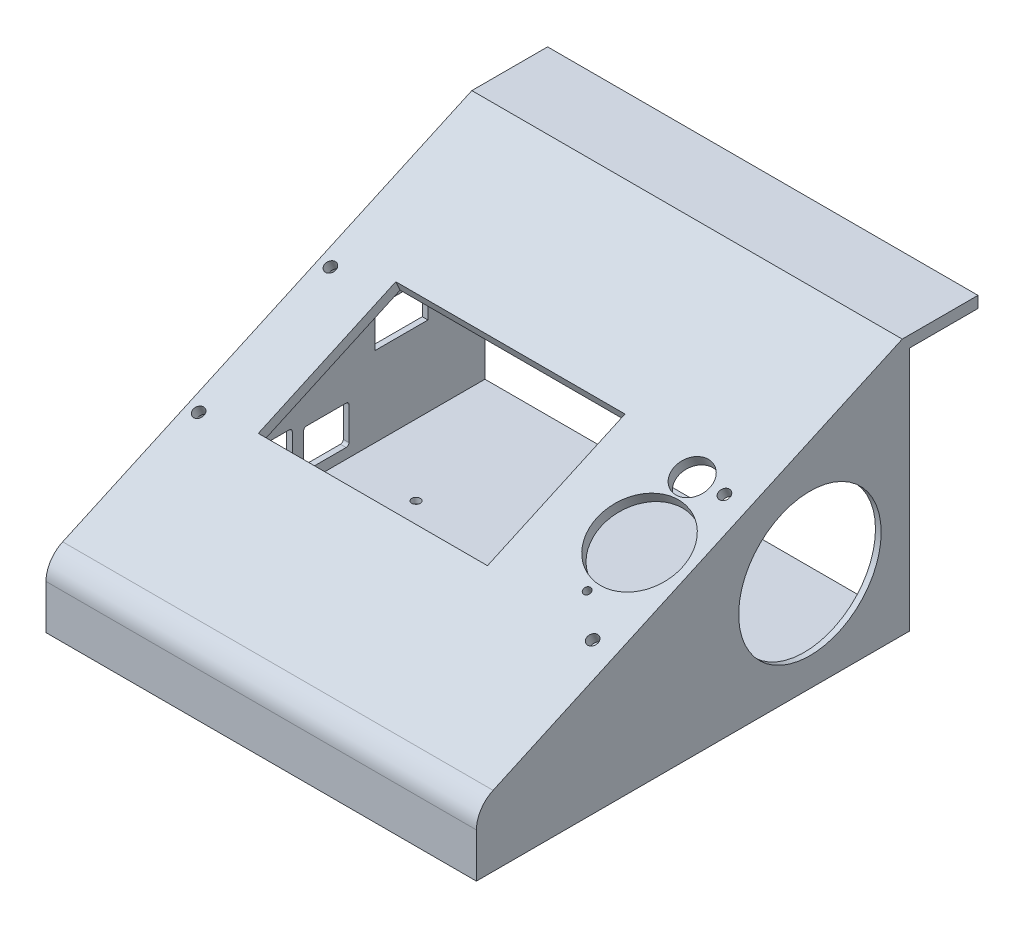
SolidWorks part; units mm, degrees
ref_plane "Front Plane" through (0, 0, 0) normal (0, 0, 1) x (1, 0, 0)
ref_plane "Top Plane" through (0, 0, 0) normal (0, 1, 0) x (1, 0, 0)
ref_plane "Right Plane" through (0, 0, 0) normal (1, 0, 0) x (0, 0, -1)
sketch "Sketch1" plane through (0, 0, 0) normal (0, 0, 1) x (1, 0, 0)
  line L0 (0, 0) -> (0, 86) construction
  dimension "D1" = 86
sketch "Sketch2" plane through (0, 0, 0) normal (0, 1, 0) x (1, 0, 0)
  line L0 (75.5, 0) -> (-75.5, 0)
  line L1 (-75.5, 0) -> (-75.5, -152)
  line L2 (-75.5, -152) -> (75.5, -152)
  line L3 (75.5, -152) -> (75.5, 0)
  point P4 (0, 0)
  dimension "D1" = 151
  dimension "D2" = 152
extrude "Boss-Extrude1" add sketch "Sketch2" along normal blind 2
sketch "Sketch3" plane through (0, 2, 0) normal (0, 1, 0) x (1, 0, 0)
  line L0 (-75.5, 0) -> (-75.5, -152) construction
  line L1 (-75.5, 0) -> (-75.5, -152)
  line L2 (-75.5, -152) -> (75.5, -152) construction
  line L3 (-75.5, -152) -> (75.5, -152)
  line L4 (75.5, -152) -> (75.5, 0) construction
  line L5 (75.5, -152) -> (75.5, 0)
extrude "Extrude-Thin1" add sketch "Sketch3" along normal blind 20 thin thin type one direction reverse wall 2
sketch "Sketch4" plane through (0, 0, 0) normal (1, 0, 0) x (0, 0, -1)
  line L0 (0, 86) -> (23.9691, 86)
  line L1 (0, 0) -> (0, 86) construction
  line L2 (23.9691, 86) -> (23.9691, 90)
  line L9 (23.9691, 90) -> (0, 90)
  line L10 (0, 90) -> (-2.6061, 90)
  line L11 (-2.6061, 90) -> (-152, 22)
  line L12 (-2.6061, 86) -> (-143.2121, 22)
  line L13 (-152, 22) -> (0, 22) construction
  line L14 (-143.2121, 22) -> (-152, 22)
  line L15 (-2.6061, 86) -> (0, 86)
  dimension "D1" = 4
  dimension "D2" = 8.7879
extrude "Boss-Extrude3" add sketch "Sketch4" against normal up to surface (151 mm away) from surface at 75.5 up to face at (-75.5, 11, 76) starting at face at (75.5, 11, 76)
sketch "Sketch6" plane through (75.5, 0, 0) normal (1, 0, 0) x (0, 0, -1)
  line L0 (0, 22) -> (-143.2121, 22)
  line L1 (-143.2121, 22) -> (-2.6061, 86)
  line L2 (-2.6061, 86) -> (0, 86)
  line L3 (0, 0) -> (0, 86) construction
  line L4 (-2.6061, 86) -> (23.9691, 86) construction
  line L5 (0, 86) -> (0, 22)
extrude "Boss-Extrude4" add sketch "Sketch6" against normal blind 2
sketch "Sketch7" plane through (-75.5, 0, 0) normal (-1, 0, 0) x (0, 0, 1)
  line L4 (0, 86) -> (0, 22)
  line L5 (0, 22) -> (143.2121, 22)
  line L6 (143.2121, 22) -> (2.6061, 86)
  line L7 (2.6061, 86) -> (0, 86)
extrude "Boss-Extrude5" add sketch "Sketch7" against normal blind 2
sketch "Sketch8" plane through (75.5, 0, 0) normal (1, 0, 0) x (0, 0, -1)
  line L0 (0, 0) -> (0, 86) construction
  line L1 (-152, 0) -> (0, 0) construction
  circle A0 centre (-35, 35) radius 25
  dimension "D1" = 50
  dimension "D2" = 35
  dimension "D3" = 35
extrude "Cut-Extrude1" cut sketch "Sketch8" against normal blind 2
sketch "Sketch9" plane through (0, 75.5364, 34.3821) normal (0, 0.9102, 0.4143) x (1, 0, 0)
  line L4 (-53.1, -19.0037) -> (27.3, -19.0037)
  line L5 (-53.1, -19.0037) -> (-53.1, -72.0037)
  line L6 (-53.1, -72.0037) -> (27.3, -72.0037)
  line L7 (-52.1, -20.0037) -> (-52.1, -71.0037)
  line L13 (-52.1, -71.0037) -> (26.3, -71.0037)
  line L14 (26.3, -71.0037) -> (26.3, -20.0037)
  line L15 (26.3, -20.0037) -> (-52.1, -20.0037)
  line L16 (-52.1, -20.0037) -> (-52.1, -71.0037) construction
  line L17 (-52.1, -71.0037) -> (26.3, -71.0037) construction
  line L18 (26.3, -71.0037) -> (26.3, -20.0037) construction
  line L19 (26.3, -20.0037) -> (-52.1, -20.0037) construction
  line L20 (27.3, -19.0037) -> (27.3, -72.0037)
  dimension "D2" = 1
  dimension "D3" = 1
  dimension "D4" = 1
  dimension "D5" = 1
  dimension "D1" = 0
sketch "Sketch10" plane through (0, 75.5364, 34.3821) normal (0, 0.9102, 0.4143) x (1, 0, 0)
  circle A0 centre (55.95, -24.5798) radius 6.25
  circle A1 centre (55.95, -24.5798) radius 6
  circle A2 centre (55.95, -24.5798) radius 6 construction
  dimension "D2" = 12.5
  dimension "D1" = 0
sketch "Sketch11" plane through (0, 75.5364, 34.3821) normal (0, 0.9102, 0.4143) x (1, 0, 0)
  circle A0 centre (57.5, -46.5798) radius 15
  circle A1 centre (57.5, -46.5798) radius 14.5
  circle A2 centre (57.5, -46.5798) radius 14.5 construction
  dimension "D2" = 30
  dimension "D1" = 0
sketch "Sketch12" plane through (0, 75.5364, 34.3821) normal (0, 0.9102, 0.4143) x (1, 0, 0)
  circle A0 centre (55.5, -64.5798) radius 1.0169 construction
  circle A1 centre (67, -24.2798) radius 1.65 construction
  circle A2 centre (67, -75.0798) radius 1.65 construction
  circle A3 centre (-71.25, -75.0798) radius 1.65 construction
  circle A4 centre (-71.25, -24.2798) radius 1.65 construction
  circle A5 centre (55.5, -64.5798) radius 1.0169 construction
  circle A6 centre (67, -24.2798) radius 1.65 construction
  circle A7 centre (67, -75.0798) radius 1.65 construction
  circle A8 centre (-71.25, -75.0798) radius 1.65 construction
  circle A9 centre (-71.25, -24.2798) radius 1.65 construction
  circle A10 centre (67, -24.2798) radius 1.9
  circle A11 centre (67, -75.0798) radius 1.9
  circle A12 centre (-71.25, -24.2798) radius 1.9
  circle A13 centre (-71.25, -75.0798) radius 1.9
  circle A14 centre (55.5, -64.5798) radius 1.27
  dimension "D1" = 3.8
  dimension "D2" = 3.8
  dimension "D3" = 3.8
  dimension "D4" = 3.8
  dimension "D5" = 2.54
extrude "Cut-Extrude6" cut sketch "Sketch9" against normal blind 10
extrude "Cut-Extrude7" cut sketch "Sketch10" against normal blind 10
extrude "Cut-Extrude8" cut sketch "Sketch11" against normal blind 10
extrude "Cut-Extrude9" cut sketch "Sketch12" against normal blind 10
fillet "Fillet2" radius 10 1 edges at (0, 22, 152)
sketch "Sketch15" plane through (-75.5, 0, 0) normal (-1, 0, 0) x (0, 0, 1)
  line L0 (0, 0) -> (0, 86) construction
  line L1 (20, 43) -> (38.5, 43)
  line L2 (20, 43) -> (20, 30)
  line L3 (20, 30) -> (38.5, 30)
  line L4 (38.5, 43) -> (38.5, 30)
  line L5 (0, 0) -> (152, 0) construction
  dimension "D1" = 18.5
  dimension "D2" = 13
  dimension "D3" = 20
  dimension "D4" = 30
extrude "Cut-Extrude12" cut sketch "Sketch15" against normal blind 10
sketch "Sketch18" plane through (-75.5, 0, 0) normal (-1, 0, 0) x (0, 0, 1)
  line L0 (48.0066, 19.1) -> (47.7066, 19.1)
  line L1 (47.7066, 19.1) -> (47.7066, 5.6)
  line L2 (48.6419, 5.6) -> (45.6419, 5.6) construction
  line L3 (47.7066, 3.425) -> (47.7066, 5.749) construction
  line L4 (47.7066, 5.6) -> (63.6066, 5.6)
  line L5 (48.6419, 5.6) -> (98.4419, 5.6) construction
  line L6 (63.6066, 3.425) -> (63.6066, 5.749) construction
  line L7 (63.6066, 5.6) -> (63.6066, 19.1)
  line L8 (63.6066, 19.1) -> (48.0066, 19.1)
  line L9 (80.1076, 20.95) -> (80.7076, 20.95)
  line L10 (80.7076, 20.95) -> (80.7076, 6.575)
  line L11 (80.7076, 7.2) -> (80.7076, 5.8693) construction
  line L12 (80.7076, 6.575) -> (67.6076, 6.5347)
  line L13 (67.6076, 5.8693) -> (67.6076, 7.2) construction
  line L14 (67.6076, 6.5347) -> (67.6076, 20.95)
  line L15 (67.6076, 20.95) -> (80.1076, 20.95)
  line L16 (98.5076, 20.95) -> (99.1076, 20.95)
  line L17 (98.5076, 20.95) -> (86.0076, 20.95)
  line L18 (86.0076, 20.95) -> (86.0076, 6.575)
  line L19 (86.0076, 5.8693) -> (86.0076, 7.2) construction
  line L20 (86.0076, 6.575) -> (99.1076, 6.575)
  line L21 (99.1076, 7.2) -> (99.1076, 5.8693) construction
  line L22 (99.1076, 6.575) -> (99.1076, 20.95)
extrude "Cut-Extrude13" cut sketch "Sketch18" against normal blind 10
fillet "Fillet5" radius 1 1 edges at (-74.5, 20.95, 99.1076)
fillet "Fillet6" radius 1 1 edges at (-74.5, 20.95, 86.0076)
fillet "Fillet7" radius 1 1 edges at (-74.5, 6.575, 86.0076)
fillet "Fillet8" radius 1 1 edges at (-74.5, 6.575, 99.1076)
fillet "Fillet9" radius 1 1 edges at (-74.5, 20.95, 80.7076)
fillet "Fillet10" radius 1 1 edges at (-74.5, 6.5347, 67.6076)
fillet "Fillet11" radius 1 1 edges at (-74.5, 20.95, 67.6076)
fillet "Fillet12" radius 1 1 edges at (-74.5, 6.575, 80.7076)
fillet "Fillet13" radius 1 1 edges at (-74.5, 19.1, 63.6066)
fillet "Fillet14" radius 1 1 edges at (-74.5, 19.1, 47.7066)
fillet "Fillet15" radius 1 1 edges at (-74.5, 5.6, 47.7066)
fillet "Fillet16" radius 1 1 edges at (-74.5, 5.6, 63.6066)
sketch "Sketch19" plane through (0, 0, 0) normal (0, -1, 0) x (1, 0, 0)
  circle A0 centre (9.3589, 98.0419) radius 1.5
  circle A1 centre (-48.6411, 98.0419) radius 1.5
  circle A2 centre (-48.6411, 49.0419) radius 1.5
  circle A3 centre (9.3589, 49.0419) radius 1.5
  dimension "D1" = 3
  dimension "D2" = 3
  dimension "D3" = 3
  dimension "D4" = 3
extrude "Cut-Extrude14" cut sketch "Sketch19" against normal blind 10
fillet "Fillet17" radius 10 1 edges at (0, 22, 143.2121)
fillet "Fillet19" radius 10.42 4 edges at (-73.5, 12, 150) (73.5, 12, 150) (0, 2, 150) (0, 22, 150)
